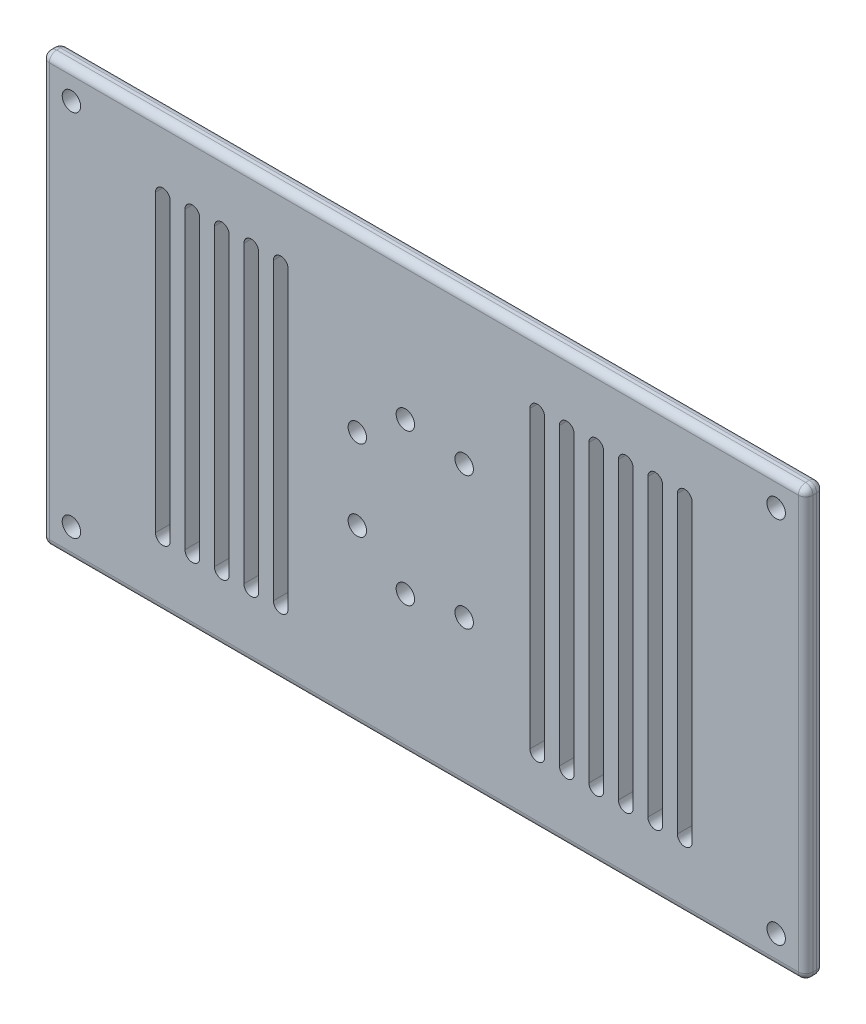
SolidWorks part; units mm, degrees
ref_plane "Plan de face" through (0, 0, 0) normal (0, 0, 1) x (1, 0, 0)
ref_plane "Plan de dessus" through (0, 0, 0) normal (0, 1, 0) x (1, 0, 0)
ref_plane "Plan de droite" through (0, 0, 0) normal (1, 0, 0) x (0, 0, -1)
sketch "Esquisse1" plane through (0, 0, 0) normal (0, 0, 1) x (1, 0, 0)
  line L1 (-51.8, 29) -> (51.8, 29)
  line L2 (-51.8, 29) -> (-51.8, -29)
  line L3 (-51.8, -29) -> (51.8, -29)
  line L4 (51.8, 29) -> (51.8, -29)
  line L5 (-51.8, 29) -> (51.8, -29) construction
  line L6 (-51.8, -29) -> (51.8, 29) construction
  point P0 (0, 0)
  point P5 (0, 0)
  point P13 (0, 0)
  dimension "D1" = 58
  dimension "D2" = 103.6
extrude "Boss.-Extru.1" add sketch "Esquisse1" along normal blind 2.5
sketch "Esquisse17" plane through (0, 0, 2.5) normal (0, 0, 1) x (1, 0, 0)
  line L1 (-2.5, 10.25) -> (2.5, 10.25)
  line L2 (-2.5, 10.25) -> (-2.5, -10.25) construction
  line L3 (-2.5, -10.25) -> (2.5, -10.25)
  line L4 (2.5, 10.25) -> (2.5, -10.25)
  line L5 (-2.5, 10.25) -> (2.5, -10.25) construction
  line L6 (-2.5, -10.25) -> (2.5, 10.25) construction
  circle A0 centre (-2.5, 10.25) radius 3
  circle A1 centre (-2.5, -10.25) radius 3
  point P0 (0, 0)
  point P9 (-2.5, -10.25)
  point P10 (-2.5, 10.25)
  dimension "D1" = 20.5
  dimension "D2" = 5
fillet "Congé3" radius 1 12 edges at (-51.8, 0, 2.5) (0, -29, 2.5) (0, 29, 2.5) (51.8, 0, 2.5) (51.8, -29, 1.25) (51.8, 29, 1.25) (-51.8, 29, 1.25) (-51.8, -29, 1.25) (51.8, 0, 0) (0, 29, 0) (-51.8, 0, 0) (0, -29, 0)
extrude "Boss.-Extru.12" add sketch "Esquisse17" against normal blind 7 contours A1 | A0
sketch "Esquisse40" plane through (0, 0, 2.5) normal (0, 0, 1) x (1, 0, 0)
  line L1 (9.0156, -5.4801) -> (5.4801, -9.0156)
  line L2 (9.0156, -5.4801) -> (-5.4801, 9.0156)
  line L3 (-5.4801, 9.0156) -> (-9.0156, 5.4801)
  line L4 (5.4801, -9.0156) -> (-9.0156, 5.4801)
  line L5 (2.5, -10.25) -> (-2.5, 10.25) construction
  line L6 (2.5, 10.25) -> (-2.5, -10.25) construction
  circle A0 centre (5.4801, -9.0156) radius 3
  circle A1 centre (-9.0156, 5.4801) radius 3
  point P0 (0, 0)
  dimension "D1" = 5
  dimension "D2" = 20.5
extrude "Boss.-Extru.8" add sketch "Esquisse40" against normal blind 7 contours A1 | A0
sketch "Esquisse42" plane through (0, 0, 2.5) normal (0, 0, 1) x (1, 0, 0)
  line L5 (-5.4801, -9.0156) -> (-9.0156, -5.4801)
  line L6 (-5.4801, -9.0156) -> (9.0156, 5.4801)
  line L7 (9.0156, 5.4801) -> (5.4801, 9.0156)
  line L8 (-9.0156, -5.4801) -> (5.4801, 9.0156)
  line L9 (2.5, -10.25) -> (-2.5, 10.25) construction
  line L10 (2.5, 10.25) -> (-2.5, -10.25) construction
  circle A0 centre (-9.0156, -5.4801) radius 3
  circle A1 centre (5.4801, 9.0156) radius 3
  point P0 (0, 0)
  dimension "D1" = 5
  dimension "D2" = 20.5
extrude "Boss.-Extru.10" add sketch "Esquisse42" against normal blind 7 contours A1 | A0
sketch "Esquisse36" plane through (0, 0, 2.5) normal (0, 0, 1) x (1, 0, 0)
  line L0 (25.4, 0) -> (0, 0) construction
  line L1 (50.8, -28) -> (50.8, 28) construction
  line L2 (50.8, 0) -> (25.4, 0) construction
  line L4 (35.4, -20) -> (15.4, -20) construction
  line L5 (35.4, -20) -> (35.4, 20) construction
  line L6 (35.4, 20) -> (15.4, 20) construction
  line L7 (15.4, -20) -> (15.4, 20) construction
  line L8 (35.4, -20) -> (15.4, 20) construction
  line L9 (35.4, 20) -> (15.4, -20) construction
  line L10 (35.4, 20) -> (35.4, -20) construction
  line L11 (36.4, 20) -> (36.4, -20)
  line L12 (34.4, 20) -> (34.4, -20)
  arc A0 (36.4, 20) -> (34.4, 20) centre (35.4, 20) ccw
  arc A1 (34.4, -20) -> (36.4, -20) centre (35.4, -20) ccw
  point P0 (25.4, 0)
  point P8 (35.4, 0)
  dimension "D1" = 20
  dimension "D2" = 40
extrude "Enlèv. mat.-Extru.2" cut sketch "Esquisse36" against normal through all
pattern_linear "Répétition linéaire1" count 6 spacing 4 along (-1, 0, 0) of "Enlèv. mat.-Extru.2"
sketch "Esquisse37" plane through (0, 0, 2.5) normal (0, 0, 1) x (1, 0, 0)
  line L0 (0, 0) -> (-50.8, 0) construction
  line L1 (-50.8, 28) -> (-50.8, -28) construction
  line L2 (-35.4, 20) -> (-35.4, -20) construction
  line L3 (-15.4, 20) -> (-35.4, 20) construction
  line L4 (-15.4, 20) -> (-15.4, -20) construction
  line L5 (-15.4, -20) -> (-35.4, -20) construction
  line L6 (-35.4, 20) -> (-35.4, -20) construction
  line L7 (-15.4, 20) -> (-35.4, -20) construction
  line L8 (-15.4, -20) -> (-35.4, 20) construction
  line L9 (-34.4, 20) -> (-34.4, -20)
  line L10 (-36.4, 20) -> (-36.4, -20)
  arc A0 (-34.4, 20) -> (-36.4, 20) centre (-35.4, 20) ccw
  arc A1 (-36.4, -20) -> (-34.4, -20) centre (-35.4, -20) ccw
  point P5 (-25.4, 0)
  point P11 (-35.4, 0)
  dimension "D1" = 40
  dimension "D2" = 20
extrude "Enlèv. mat.-Extru.3" cut sketch "Esquisse37" against normal through all
pattern_linear "Répétition linéaire2" count 5 spacing 4 along (1, 0, 0) of "Enlèv. mat.-Extru.3"
hole_wizard "Trou pour taraudage pour trou taraudé M38" positions "Esquisse3D10" profile "Esquisse41" hole size "M3" standard "AS"
sketch3d "Esquisse3D10"
  point P0 (5.4801, -9.0156, 2.5)
  point P3 (-9.0156, 5.4801, 2.5)
sketch "Esquisse41" plane through (5.4801, -9.0156, 2.5) normal (1, 0, 0) x (0, -1, 0)
  line L0 (0, 0) -> (0, 5.7511)
  line L1 (0, 5.7511) -> (1.25, 5)
  line L2 (1.25, 5) -> (1.25, 0)
  line L5 (1.25, 0) -> (0, 0)
  line L10 (0, 5.7511) -> (-1.25, 5) construction
  line L11 (0, -6.35) -> (0, 107.95) construction
  dimension "Diamètre du perçage" = 2.5
  dimension "Profondeur du perçage" = 5
  dimension "Angle de pointe" = 118
hole_wizard "Trou pour taraudage pour trou taraudé M39" positions "Esquisse3D11" profile "Esquisse43" hole size "M3" standard "AS"
sketch3d "Esquisse3D11"
  point P0 (5.4801, 9.0156, 2.5)
  point P3 (-9.0156, -5.4801, 2.5)
sketch "Esquisse43" plane through (5.4801, 9.0156, 2.5) normal (1, 0, 0) x (0, -1, 0)
  line L0 (0, 0) -> (0, 5.7511)
  line L1 (0, 5.7511) -> (1.25, 5)
  line L2 (1.25, 5) -> (1.25, 0)
  line L5 (1.25, 0) -> (0, 0)
  line L10 (0, 5.7511) -> (-1.25, 5) construction
  line L11 (0, -6.35) -> (0, 107.95) construction
  dimension "Diamètre du perçage" = 2.5
  dimension "Profondeur du perçage" = 5
  dimension "Angle de pointe" = 118
hole_wizard "Trou pour taraudage pour trou taraudé M311" positions "Esquisse3D15" profile "Esquisse47" hole size "M3" standard "AS"
sketch3d "Esquisse3D15"
  point P0 (-2.5, 10.25, 2.5)
  point P3 (-2.5, -10.25, 2.5)
sketch "Esquisse47" plane through (-2.5, 10.25, 2.5) normal (1, 0, 0) x (0, -1, 0)
  line L0 (0, 0) -> (0, 5.7511)
  line L1 (0, 5.7511) -> (1.25, 5)
  line L2 (1.25, 5) -> (1.25, 0)
  line L5 (1.25, 0) -> (0, 0)
  line L10 (0, 5.7511) -> (-1.25, 5) construction
  line L11 (0, -6.35) -> (0, 107.95) construction
  dimension "Diamètre du perçage" = 2.5
  dimension "Profondeur du perçage" = 5
  dimension "Angle de pointe" = 118
fillet "Congé4" radius 0.5 12 edges at (0.5, -10.25, 0) (0.5, -10.25, -4.5) (0.5, 10.25, 0) (0.5, 10.25, -4.5) (8.4801, -9.0156, -4.5) (8.4801, 9.0156, -4.5) (-6.0156, 5.4801, 0) (-6.0156, 5.4801, -4.5) (-6.0156, -5.4801, 0) (-6.0156, -5.4801, -4.5) (8.4801, 9.0156, 0) (8.4801, -9.0156, 0)
sketch "Esquisse48" plane through (0, 0, 2.5) normal (0, 0, 1) x (1, 0, 0)
  line L0 (51.8, 28) -> (51.8, -28) construction
  line L1 (-50.8, 29) -> (50.8, 29) construction
  line L2 (50.8, -29) -> (-50.8, -29) construction
  line L3 (-50.8, -29) -> (50.8, -29) construction
  line L6 (-51.8, -28) -> (-51.8, 28) construction
  circle A0 centre (-47.8, 25) radius 3
  circle A1 centre (-47.8, -25) radius 3
  circle A2 centre (47.8, 25) radius 3.3164
  circle A3 centre (47.8, -25) radius 3.4515
  point P18 (-52.3772, -26.2315)
  point P21 (0, 0)
  point P22 (0, 0)
  point P23 (0, 0)
  dimension "D1" = 4
  dimension "D2" = 4
  dimension "D3" = 4
  dimension "D4" = 4
  dimension "D5" = 4
  dimension "D6" = 4
  dimension "D7" = 4
  dimension "D8" = 4
hole_wizard "Trou pour taraudage pour trou taraudé M312" positions "Esquisse3D16" profile "Esquisse49" hole size "M3" standard "AS"
sketch3d "Esquisse3D16"
  point P0 (-47.8, 25, 2.5)
  point P3 (-47.8, -25, 2.5)
  point P6 (47.8, -25, 2.5)
  point P9 (47.8, 25, 2.5)
sketch "Esquisse49" plane through (-47.8, 25, 2.5) normal (1, 0, 0) x (0, -1, 0)
  line L0 (0, 0) -> (0, 5.7511)
  line L1 (0, 5.7511) -> (1.25, 5)
  line L2 (1.25, 5) -> (1.25, 0)
  line L5 (1.25, 0) -> (0, 0)
  line L10 (0, 5.7511) -> (-1.25, 5) construction
  line L11 (0, -6.35) -> (0, 107.95) construction
  dimension "Diamètre du perçage" = 2.5
  dimension "Profondeur du perçage" = 5
  dimension "Angle de pointe" = 118
